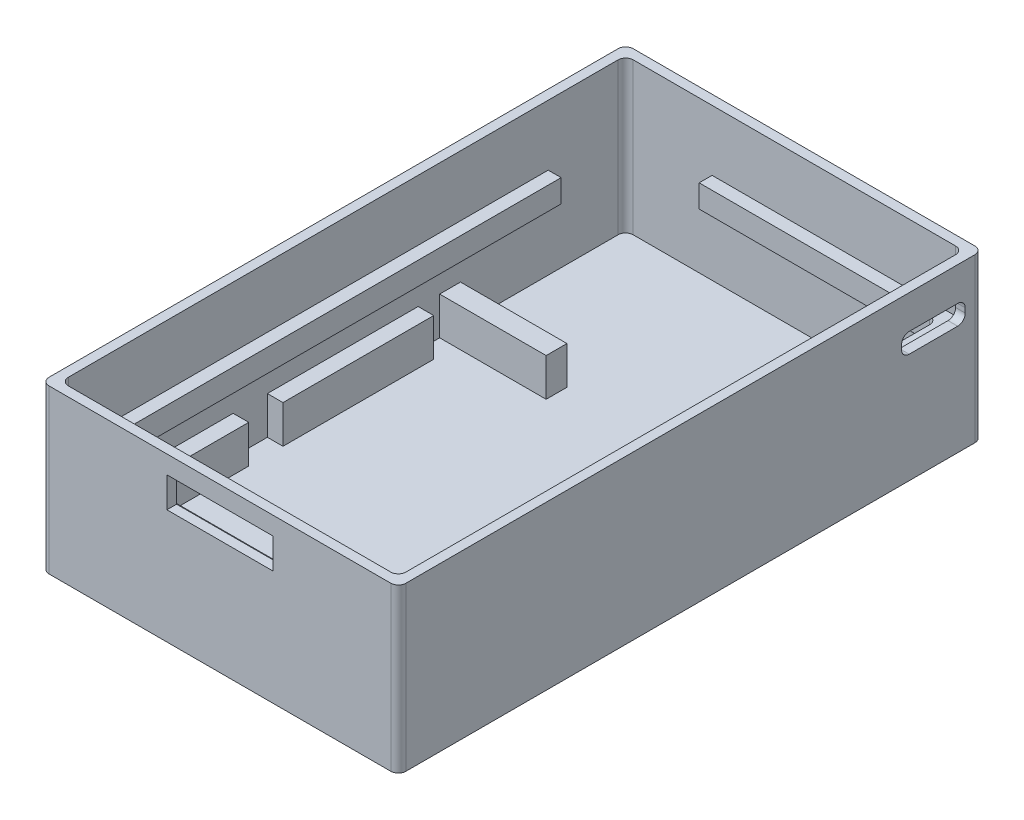
SolidWorks part; units mm, degrees
ref_plane "Front Plane" through (0, 0, 0) normal (0, 0, 1) x (1, 0, 0)
ref_plane "Top Plane" through (0, 0, 0) normal (0, 1, 0) x (1, 0, 0)
ref_plane "Right Plane" through (0, 0, 0) normal (1, 0, 0) x (0, 0, -1)
sketch "Sketch1" plane through (0, 0, 0) normal (0, 1, 0) x (1, 0, 0)
  line L5 (0, 0) -> (47.0912, 0)
  line L6 (0, 0) -> (0, -77.0912)
  line L7 (0, -77.0912) -> (47.0912, -77.0912)
  line L8 (47.0912, 0) -> (47.0912, -77.0912)
extrude "Boss-Extrude1" add sketch "Sketch1" along normal blind 1.5
sketch "Sketch2" plane through (0, 1.5, 0) normal (0, 1, 0) x (1, 0, 0)
  line L3 (1.2728, -1.2728) -> (45.8184, -1.2728)
  line L4 (1.2728, -1.2728) -> (1.2728, -75.8184)
  line L5 (1.2728, -75.8184) -> (45.8184, -75.8184)
  line L6 (45.8184, -1.2728) -> (45.8184, -75.8184)
  line L7 (0, 0) -> (47.0912, 0)
  line L8 (0, 0) -> (0, -77.0912)
  line L9 (0, -77.0912) -> (47.0912, -77.0912)
  line L10 (47.0912, 0) -> (47.0912, -77.0912)
extrude "Boss-Extrude2" add sketch "Sketch2" along normal blind 20
fillet "Fillet4" radius 1 8 edges at (45.8184, 11.5, 1.2728) (1.2728, 11.5, 1.2728) (45.8184, 11.5, 75.8184) (1.2728, 11.5, 75.8184) (47.0912, 10.75, 0) (0, 10.75, 0) (47.0912, 10.75, 77.0912) (0, 10.75, 77.0912)
sketch "Sketch3" plane through (0, 1.5, 0) normal (0, 1, 0) x (1, 0, 0)
  line L1 (2.2728, -2.2728) -> (44.8184, -2.2728)
  line L2 (2.2728, -2.2728) -> (2.2728, -74.8184)
  line L3 (2.2728, -74.8184) -> (44.8184, -74.8184)
  line L4 (44.8184, -2.2728) -> (44.8184, -74.8184)
sketch "Sketch9" plane through (47.0912, 0, 0) normal (1, 0, 0) x (0, 0, -1)
  line L1 (-10.6717, 14.4646) -> (-2.2717, 14.4646)
  line L2 (-10.6717, 14.4646) -> (-10.6717, 17.0646)
  line L3 (-10.6717, 17.0646) -> (-2.2717, 17.0646)
  line L4 (-2.2717, 14.4646) -> (-2.2717, 17.0646)
  line L6 (-2.2717, 14.4646) -> (-10.3095, 14.4646)
extrude "Cut-Extrude4" cut sketch "Sketch9" against normal blind 2 contours L1 L4 L3 L2 region at (47.0912, 15.7646, 6.4717)
fillet "Fillet5" radius 1 4 edges at (46.4548, 17.0646, 10.6717) (46.4548, 14.4646, 2.2717) (46.4548, 17.0646, 2.2717) (46.4548, 14.4646, 10.6717)
sketch "Sketch10" plane through (0, 1.5, 0) normal (0, 1, 0) x (1, 0, 0)
  line L35 (3.3328, -72.9737) -> (0.8328, -72.9737)
  line L36 (3.3328, -72.9737) -> (3.3328, -53.078)
  line L37 (3.3328, -53.078) -> (0.8328, -53.078)
  line L38 (0.8328, -72.9737) -> (0.8328, -53.078)
  line L47 (0.3249, -25.8184) -> (15.3249, -25.8184)
  line L48 (0.3249, -25.8184) -> (0.3249, -23.0714)
  line L49 (0.3249, -23.0714) -> (15.3249, -23.0714)
  line L50 (15.3249, -25.8184) -> (15.3249, -23.0714)
  line L52 (31.7448, -25.8184) -> (31.7448, -23.0714)
  line L53 (46.7448, -23.0714) -> (31.7448, -23.0714)
  line L54 (46.7448, -25.8184) -> (46.7448, -23.0714)
  line L55 (46.7448, -25.8184) -> (31.7448, -25.8184)
  line L71 (0.8328, -28.6631) -> (0.8328, -48.5587)
  line L72 (3.3328, -48.5587) -> (0.8328, -48.5587)
  line L73 (3.3328, -28.6631) -> (3.3328, -48.5587)
  line L74 (3.3328, -28.6631) -> (0.8328, -28.6631)
  line L75 (44.0456, -28.6631) -> (46.5456, -28.6631)
  line L76 (44.0456, -28.6631) -> (44.0456, -48.5587)
  line L77 (44.0456, -48.5587) -> (46.5456, -48.5587)
  line L78 (46.5456, -28.6631) -> (46.5456, -48.5587)
  line L79 (46.5456, -72.9737) -> (46.5456, -53.078)
  line L80 (44.0456, -53.078) -> (46.5456, -53.078)
  line L81 (44.0456, -72.9737) -> (44.0456, -53.078)
  line L82 (44.0456, -72.9737) -> (46.5456, -72.9737)
extrude "Boss-Extrude4" add sketch "Sketch10" along normal blind 5
sketch "Sketch11" plane through (0, 0, 77.0912) normal (0, 0, 1) x (1, 0, 0)
  line L2 (16.5456, 19.1179) -> (16.5456, 15.1179)
  line L7 (16.5456, 19.1179) -> (30.5456, 19.1179)
  line L9 (16.5456, 15.1179) -> (30.5456, 15.1179)
  line L10 (30.5456, 19.1179) -> (30.5456, 15.1179)
extrude "Cut-Extrude5" cut sketch "Sketch11" against normal blind 10
sketch "Sketch12" plane through (47.0912, 0, 0) normal (1, 0, 0) x (0, 0, -1)
  line L0 (-1, 0) -> (-1, 21.5) construction
  line L6 (-76.0912, 10.5) -> (-1, 10.5)
  line L7 (-76.0912, 10.5) -> (-76.0912, 13.5)
  line L8 (-76.0912, 13.5) -> (-1, 13.5)
  line L9 (-1, 10.5) -> (-1, 13.5)
extrude "Boss-Extrude5" add sketch "Sketch12" against normal blind 46 contours L8 L9 L6 L7
sketch "Sketch13" plane through (0, 13.5, 0) normal (0, 1, 0) x (1, 0, 0)
  line L4 (2.9799, -74.1113) -> (44.1113, -74.1113)
  line L7 (2.9799, -74.1113) -> (2.9799, -2.9799)
  line L8 (2.9799, -2.9799) -> (44.1113, -2.9799)
  line L9 (44.1113, -74.1113) -> (44.1113, -2.9799)
  point P0 (0, 0)
extrude "Cut-Extrude6" cut sketch "Sketch13" against normal blind 3 contours L7 L8 L9 L4
fillet "Fillet6" radius 1 4 edges at (2.9799, 12, 74.1113) (44.1113, 12, 74.1113) (44.1113, 12, 2.9799) (2.9799, 12, 2.9799)
sketch "Sketch14" plane through (0, 13.5, 0) normal (0, 1, 0) x (1, 0, 0)
  line L0 (1.2728, -2.2728) -> (1.2728, -74.8184) construction
  line L1 (1.2728, -11.4922) -> (12.6792, -11.4922)
  line L4 (12.6792, -11.4922) -> (12.6792, -1.2728)
  line L5 (2.2728, -1.2728) -> (44.8184, -1.2728) construction
  line L6 (12.6792, -1.2728) -> (2.2728, -1.2728)
  line L7 (1.2728, -11.4922) -> (1.2728, -2.2728)
  arc A0 (1.2728, -2.2728) -> (2.2728, -1.2728) centre (2.2728, -2.2728) cw
extrude "Cut-Extrude8" cut sketch "Sketch14" against normal blind 3 contours L4 L6 A0 L7 L1
